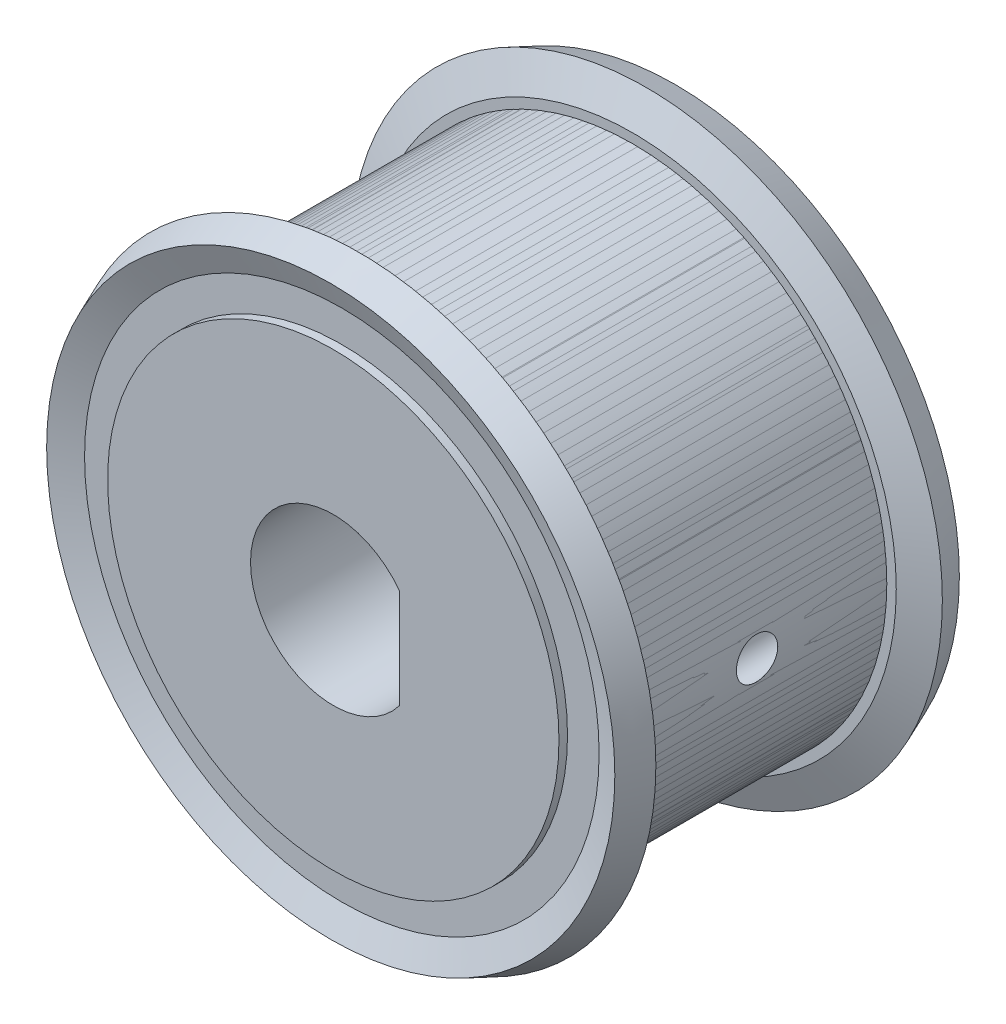
SolidWorks part; units mm, degrees
material "6061 合金"
ref_plane "前视基准面" through (0, 0, 0) normal (0, 0, 1) x (1, 0, 0)
ref_plane "上视基准面" through (0, 0, 0) normal (0, 1, 0) x (1, 0, 0)
ref_plane "右视基准面" through (0, 0, 0) normal (1, 0, 0) x (0, 0, -1)
ref_axis "基准轴1" through (0, 0, 55) along (0, 0, -1)
sketch "SketchRevolveGearBelt01" plane through (0, 0, 0) normal (1, 0, 0) x (0, 0, -1)
  line L0 (0, 0) -> (1, 0) construction
  line L1 (10.2489, 0) -> (10.2489, 13.6295)
  line L2 (10.2489, 13.6295) -> (9.7333, 13.6295)
  line L3 (9.7333, 13.6295) -> (9.7333, 15.5381)
  line L4 (9.7333, 15.5381) -> (10.4042, 17.1579)
  line L5 (10.4042, 17.1579) -> (8.6513, 17.884)
  line L6 (8.6513, 17.884) -> (7.8359, 15.9155)
  line L7 (7.8359, 15.9155) -> (7.8359, 15.344)
  line L8 (7.8359, 15.344) -> (-7.8359, 15.344)
  line L9 (-7.8359, 15.344) -> (-7.8359, 15.9155)
  line L10 (-7.8359, 15.9155) -> (-8.6513, 17.884)
  line L11 (-8.6513, 17.884) -> (-10.4042, 17.1579)
  line L12 (-10.4042, 17.1579) -> (-9.7333, 15.5381)
  line L13 (-9.7333, 15.5381) -> (-9.7333, 13.6295)
  line L14 (-9.7333, 13.6295) -> (-10.2489, 13.6295)
  line L15 (-10.2489, 13.6295) -> (-10.2489, 0)
  line L16 (-10.2489, 0) -> (10.2489, 0)
  dimension "GearBeltFlange1OutsideLength" = 1.9086
  dimension "GearBeltFlange1X" = 0.6709
  dimension "GearBeltFlange1Y" = 1.6198
  dimension "GearBeltFlangeThickness" = 1.8974
  dimension "GearBeltFlangeInside" = 0.5715
  dimension "GearBeltOutsideDiameter" = 15.344
  dimension "GearBeltFlange2X" = 0.6709
revolve "GearBelt01" add sketch "SketchRevolveGearBelt01" angle 360 about L0
sketch "SketchToothGearBelt01" plane through (0, 0, 0) normal (0, 0, 1) x (1, 0, 0)
  arc A0 (15.1892, 2.17) -> (15.1892, -2.17) centre (0, 0) cw
  spline S0 degree 3 poles (15.1892, -2.17) (15.1933, -2.1413) (15.1958, -2.0978) (15.1916, -2.0399) (15.1848, -1.997) (15.1743, -1.9547) (15.1603, -1.9136) (15.1428, -1.8738) (15.1219, -1.8356) (15.0979, -1.7993) (15.0709, -1.7653) (15.041, -1.7336) (15.0086, -1.7046) (14.9738, -1.6785) (14.9369, -1.6555) (14.8981, -1.6357) (14.8578, -1.6193) (14.8163, -1.6064) (14.7738, -1.5971) (14.7307, -1.5914) (14.6736, -1.5894) (14.5978, -1.5908) (14.5033, -1.5873) (14.4043, -1.5753) (14.3065, -1.5557) (14.2106, -1.5285) (14.1171, -1.4939) (14.0266, -1.452) (13.9397, -1.4032) (13.8569, -1.3477) (13.7786, -1.2859) (13.7055, -1.2181) (13.6379, -1.1449) (13.5762, -1.0665) (13.5209, -0.9836) (13.4722, -0.8965) (13.4305, -0.806) (13.396, -0.7124) (13.369, -0.6164) (13.3496, -0.5186) (13.3376, -0.4196) (13.3342, -0.2999) (13.3356, -0.16) (13.3351, 0) (13.3356, 0.16) (13.3342, 0.2999) (13.3376, 0.4196) (13.3496, 0.5186) (13.369, 0.6164) (13.396, 0.7124) (13.4305, 0.806) (13.4722, 0.8965) (13.5209, 0.9836) (13.5762, 1.0665) (13.6379, 1.1449) (13.7055, 1.2181) (13.7786, 1.2859) (13.8569, 1.3477) (13.9397, 1.4032) (14.0266, 1.452) (14.1171, 1.4939) (14.2106, 1.5285) (14.3065, 1.5557) (14.4043, 1.5753) (14.5033, 1.5873) (14.5978, 1.5908) (14.6736, 1.5894) (14.7307, 1.5914) (14.7738, 1.5971) (14.8163, 1.6064) (14.8578, 1.6193) (14.8981, 1.6357) (14.9369, 1.6555) (14.9738, 1.6785) (15.0086, 1.7046) (15.041, 1.7336) (15.0709, 1.7653) (15.0979, 1.7993) (15.1219, 1.8356) (15.1428, 1.8738) (15.1603, 1.9136) (15.1743, 1.9547) (15.1848, 1.997) (15.1916, 2.0399) (15.1958, 2.0978) (15.1933, 2.1413) (15.1892, 2.17) knots 0 0 0 0 0.013305 0.019957 0.026609 0.033261 0.039914 0.046566 0.053218 0.059871 0.066523 0.073175 0.079828 0.08648 0.093132 0.099784 0.106437 0.113089 0.119741 0.126394 0.133046 0.145958 0.16121 0.176462 0.191714 0.206966 0.222218 0.23747 0.252722 0.267974 0.283226 0.298478 0.31373 0.328983 0.344235 0.359487 0.374739 0.389991 0.405243 0.420495 0.435747 0.450999 0.4755 0.5 0.5245 0.549001 0.564253 0.579505 0.594757 0.610009 0.625261 0.640513 0.655765 0.671017 0.68627 0.701522 0.716774 0.732026 0.747278 0.76253 0.777782 0.793034 0.808286 0.823538 0.83879 0.854042 0.866954 0.873606 0.880259 0.886911 0.893563 0.900216 0.906868 0.91352 0.920172 0.926825 0.933477 0.940129 0.946782 0.953434 0.960086 0.966739 0.973391 0.980043 0.986695 1 1 1 1
extrude "ToothExtrudeCutGearBelt01" cut sketch "SketchToothGearBelt01" against normal blind 7.8359 and the other way blind 7.8359
pattern_circular "PatternGearBelt01" count 20 every 18 about axis through (0, 0, 55) along (0, 0, -1) of "ToothExtrudeCutGearBelt01"
sketch "AuxiliarySketchGearBelt01" plane through (0, 0, 0) normal (0, 0, 1) x (1, 0, 0)
  circle A0 centre (0, 0) radius 15.9155 construction
  dimension "PitchDiameter" = 31.831
sketch "草图5" plane through (0, 0, 10.2489) normal (0, 0, 1) x (1, 0, 0)
  line L0 (4, 3) -> (4, -3)
  circle A0 centre (0, 0) radius 5
  dimension "D1" = 10
  dimension "D2" = 4
extrude "切除-拉伸2" cut sketch "草图5" against normal through all and the other way through all contours L0 A0 region at (-0.2418, 0, 10.2489)
sketch "草图8" plane through (4, 0, 0) normal (-1, 0, 0) x (0, 0, 1)
  point P0 (0, 0)
hole_wizard "M3 螺纹孔1" positions "3D草图1" profile "草图9" tap size "M3" standard "GB" end condition through all
sketch3d "3D草图1"
  point P0 (4, 0, 0)
sketch "草图9" plane through (4, 0, 0) normal (0, 1, 0) x (0, 0, 1)
  line L0 (0, 0) -> (0, 13.884)
  line L1 (0, 13.884) -> (1.25, 13.884)
  line L2 (1.25, 13.884) -> (1.25, 0)
  line L5 (1.25, 0) -> (0, 0)
  line L11 (0, -6.35) -> (0, 107.95) construction
  dimension "螺纹线主直径" = 2.5
  dimension "通孔螺纹孔钻头深度" = 13.884
